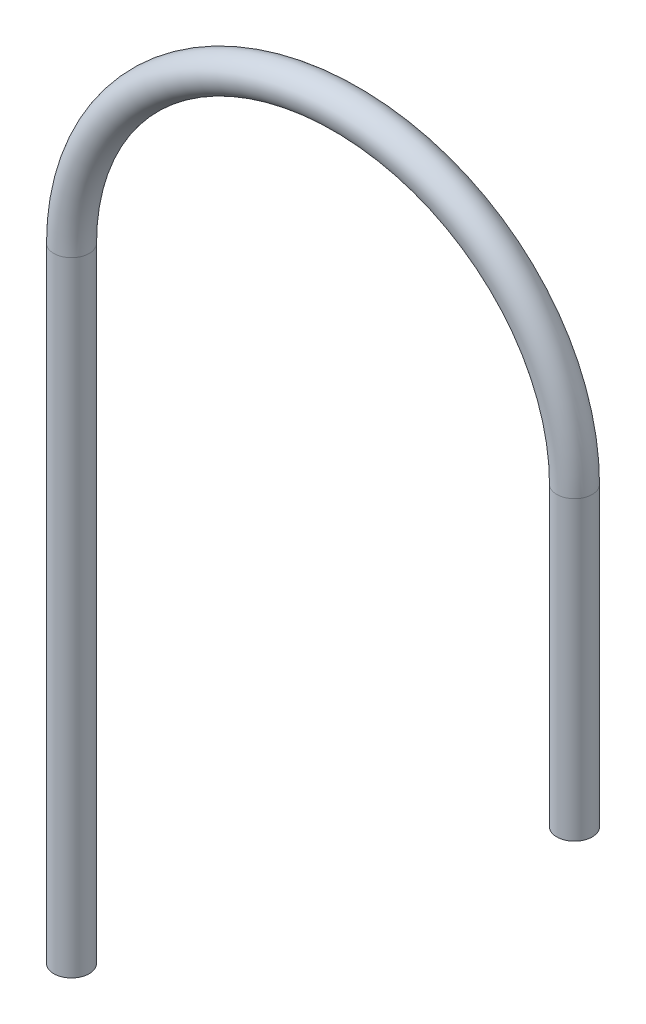
SolidWorks part; units mm, degrees
material "PE faible/moyenne densité"
ref_plane "Front" through (0, 0, 0) normal (0, 0, 1) x (1, 0, 0)
ref_plane "Top" through (0, 0, 0) normal (0, 1, 0) x (1, 0, 0)
ref_plane "Right" through (0, 0, 0) normal (1, 0, 0) x (0, 0, -1)
sketch3d "Esquisse3D2"
  line L0 (42, 165, -59.25) -> (42, 215.275, -59.25)
  line L1 (-36, 215.275, -52) -> (-36, 109.55, -52)
  arc A0 (42, 215.275, -59.25) -> (-36, 215.275, -52) centre (3, 215.275, -55.625) ccw
  circle A1 centre (-36, 117.55, -52) radius 1.1 construction
  point P3 (6.625, 215.275, -16.625)
  point P9 (-36, 116.45, -52)
  dimension "D4" = 105.725
  dimension "D1" = 165
  dimension "D2" = 59.25
  dimension "D3" = 42
  dimension "D5" = 109.55
sweep "Balayage-Mince1" add path "Esquisse3D2" circular profile diameter 6 parameters "D1"=1, "D3"=6
equation "\"D4@Esquisse3D2\"=120-((\"D5@Esquisse3D2\"-81)/2)"
